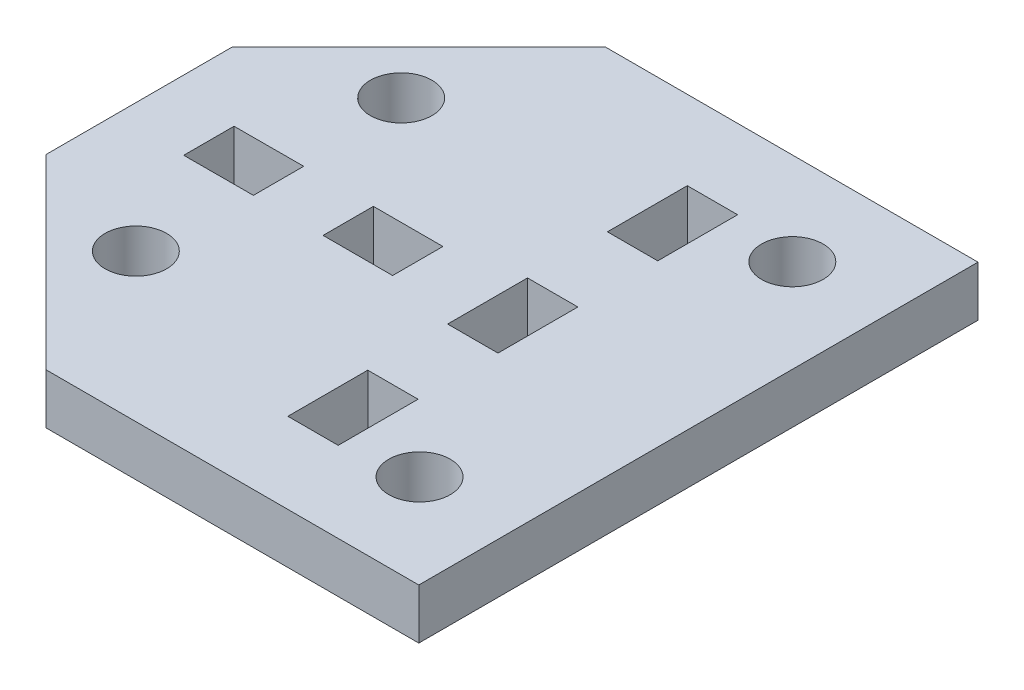
SolidWorks part; units mm, degrees
ref_plane "Ön Düzlem" through (0, 0, 0) normal (0, 0, 1) x (1, 0, 0)
ref_plane "Üst Düzlem" through (0, 0, 0) normal (0, 1, 0) x (1, 0, 0)
ref_plane "Sağ Düzlem" through (0, 0, 0) normal (1, 0, 0) x (0, 0, -1)
sketch "Sketch1" plane through (0, 0, 0) normal (0, 1, 0) x (1, 0, 0)
  line L0 (10.7767, -15.9461) -> (-9.2233, -15.9461)
  line L1 (10.7767, -15.9461) -> (10.7767, 14.0539)
  line L2 (10.7767, 14.0539) -> (-9.2233, 14.0539)
  line L4 (10.7767, -15.9461) -> (-9.2233, 14.0539) construction
  line L5 (10.7767, 14.0539) -> (-9.2233, -15.9461) construction
  line L14 (2.1267, -11.6204) -> (2.1267, -7.3347)
  line L16 (-19.2233, 4.0539) -> (-9.2233, 14.0539)
  line L17 (-9.2233, -15.9461) -> (-19.2233, -5.9461)
  line L18 (2.1267, -3.049) -> (2.1267, 1.2367)
  line L19 (-19.2233, 4.0539) -> (-19.2233, -5.9461)
  line L20 (2.1267, 5.5224) -> (2.1267, 9.8081)
  line L22 (-0.5733, -11.6204) -> (-0.5733, -7.3347)
  line L24 (-0.5733, -3.049) -> (-0.5733, 1.2367)
  line L26 (-0.5733, 5.5224) -> (-0.5733, 9.8081)
  line L28 (-0.5733, -11.6204) -> (2.1267, -11.6204)
  line L29 (-0.5733, -7.3347) -> (2.1267, -7.3347)
  line L30 (2.1267, -3.049) -> (-0.5733, -3.049)
  line L31 (-0.5733, 1.2367) -> (2.1267, 1.2367)
  line L32 (2.1267, 5.5224) -> (-0.5733, 5.5224)
  line L33 (-0.5733, 9.8081) -> (2.1267, 9.8081)
  line L34 (-15.4933, 0.4119) -> (-11.7633, 0.4199)
  line L36 (-8.0333, 0.4279) -> (-4.3033, 0.4279)
  line L38 (-15.4933, -2.2881) -> (-11.7633, -2.2801)
  line L40 (-8.0333, -2.2721) -> (-4.3033, -2.2721)
  line L42 (-15.4933, -2.2881) -> (-15.4933, 0.4119)
  line L43 (-11.7633, -2.2801) -> (-11.7633, 0.4199)
  line L44 (-8.0333, 0.4279) -> (-8.0333, -2.2721)
  line L45 (-4.3033, 0.4279) -> (-4.3033, -2.2721)
  circle A0 centre (-12.3262, -8.023) radius 1.65
  circle A1 centre (5.7767, -10.9062) radius 1.65
  circle A2 centre (5.7767, 9.0938) radius 1.65
  circle A5 centre (-12.3262, 6.2107) radius 1.65
  point P0 (0.7767, -0.9461)
  dimension "D1" = 30
  dimension "D2" = 20
extrude "Boss-Extrude1" add sketch "Sketch1" against normal blind 2.7
